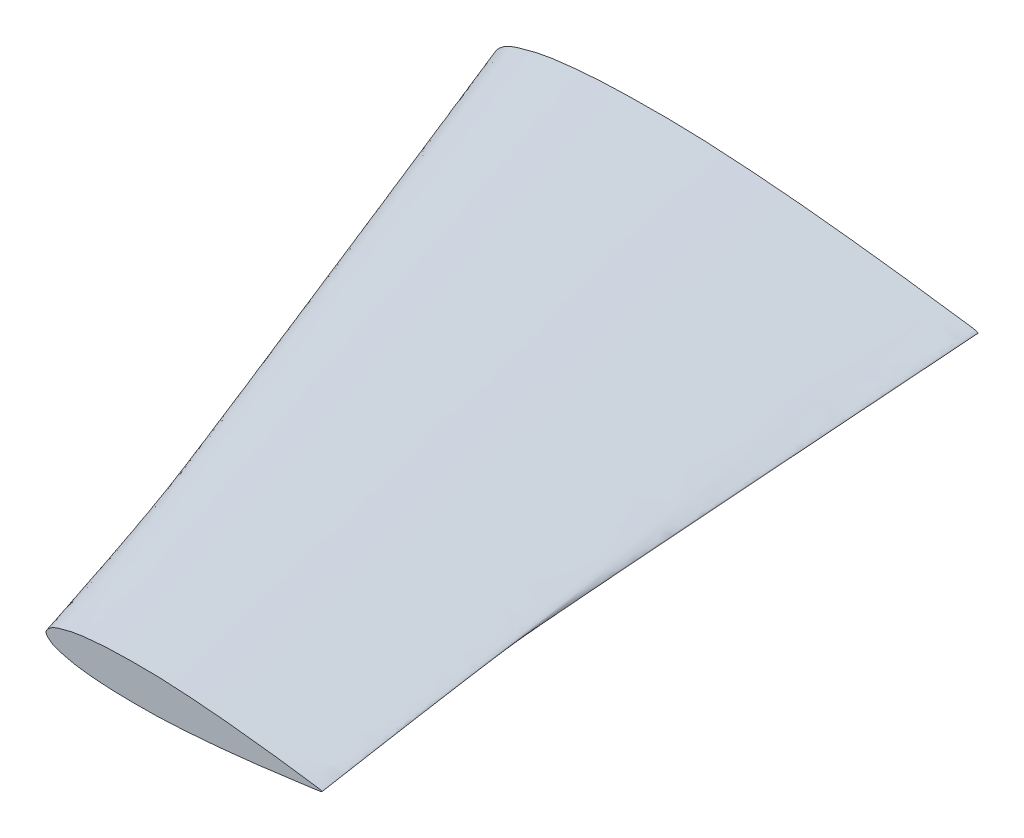
SolidWorks part; units mm, degrees
ref_plane "Front Plane" through (0, 0, 0) normal (0, 0, 1) x (1, 0, 0)
ref_plane "Top Plane" through (0, 0, 0) normal (0, 1, 0) x (1, 0, 0)
ref_plane "Right Plane" through (0, 0, 0) normal (1, 0, 0) x (0, 0, -1)
curve "Curve5"
  spline degree 3 poles (23.9448, -0.2408, 0) (26.1299, 0, 0) (23.9448, 0.2408, 0) (22.5461, 0.4603, 0) (20.2857, 0.7456, 0) (17.7917, 1.0324, 0) (15.2403, 1.2957, 0) (12.7026, 1.4795, 0) (10.1615, 1.6247, 0) (7.6196, 1.6225, 0) (5.4998, 1.5726, 0) (3.8069, 1.4161, 0) (2.7453, 1.2841, 0) (1.8994, 1.0976, 0) (1.2662, 0.917, 0) (0.7044, 0.7371, 0) (0.2766, 0.4441, 0) (-0.1637, 0, 0) (0.2766, -0.4441, 0) (0.7044, -0.7371, 0) (1.2662, -0.917, 0) (1.8994, -1.0976, 0) (2.7453, -1.2841, 0) (3.8069, -1.4161, 0) (5.4998, -1.5726, 0) (7.6196, -1.6225, 0) (10.1615, -1.6247, 0) (12.7026, -1.4795, 0) (15.2403, -1.2957, 0) (17.7917, -1.0324, 0) (20.2857, -0.7456, 0) (22.5461, -0.4603, 0) (23.9448, -0.2408, 0) (26.1299, 0, 0) (23.9448, 0.2408, 0) knots -0.099106 -0.049663 -0.024909 0 0.024909 0.049663 0.099106 0.148459 0.197734 0.246901 0.295993 0.345023 0.394083 0.418697 0.443452 0.456002 0.468731 0.481844 0.489255 0.5 0.510745 0.518156 0.531269 0.543998 0.556548 0.581303 0.605917 0.654977 0.704007 0.753099 0.802266 0.851541 0.900894 0.950337 0.975091 1 1.024909 1.049663 1.099106 periodic
sketch "Sketch2" plane through (0, 0, 0) normal (0, 0, 1) x (1, 0, 0)
  line L0 (0, 0) -> (177.8, 0) construction
  spline S0 degree 3 poles (23.9448, -0.2408) (26.1299, 0) (23.9448, 0.2408) (22.5461, 0.4603) (20.2857, 0.7456) (17.7917, 1.0324) (15.2403, 1.2957) (12.7026, 1.4795) (10.1615, 1.6247) (7.6196, 1.6225) (5.4998, 1.5726) (3.8069, 1.4161) (2.7453, 1.2841) (1.8994, 1.0976) (1.2662, 0.917) (0.7044, 0.7371) (0.2766, 0.4441) (-0.1637, 0) (0.2766, -0.4441) (0.7044, -0.7371) (1.2662, -0.917) (1.8994, -1.0976) (2.7453, -1.2841) (3.8069, -1.4161) (5.4998, -1.5726) (7.6196, -1.6225) (10.1615, -1.6247) (12.7026, -1.4795) (15.2403, -1.2957) (17.7917, -1.0324) (20.2857, -0.7456) (22.5461, -0.4603) (23.9448, -0.2408) (26.1299, 0) (23.9448, 0.2408) knots -0.099106 -0.049663 -0.024909 0 0.024909 0.049663 0.099106 0.148459 0.197734 0.246901 0.295993 0.345023 0.394083 0.418697 0.443452 0.456002 0.468731 0.481844 0.489255 0.5 0.510745 0.518156 0.531269 0.543998 0.556548 0.581303 0.605917 0.654977 0.704007 0.753099 0.802266 0.851541 0.900894 0.950337 0.975091 1 1.024909 1.049663 1.099106 only from (25.4, 0) to (25.4, 0) construction
  spline S1 degree 3 poles (23.9448, -0.2408) (26.1299, 0) (23.9448, 0.2408) (22.5461, 0.4603) (20.2857, 0.7456) (17.7917, 1.0324) (15.2403, 1.2957) (12.7026, 1.4795) (10.1615, 1.6247) (7.6196, 1.6225) (5.4998, 1.5726) (3.8069, 1.4161) (2.7453, 1.2841) (1.8994, 1.0976) (1.2662, 0.917) (0.7044, 0.7371) (0.2766, 0.4441) (-0.1637, 0) (0.2766, -0.4441) (0.7044, -0.7371) (1.2662, -0.917) (1.8994, -1.0976) (2.7453, -1.2841) (3.8069, -1.4161) (5.4998, -1.5726) (7.6196, -1.6225) (10.1615, -1.6247) (12.7026, -1.4795) (15.2403, -1.2957) (17.7917, -1.0324) (20.2857, -0.7456) (22.5461, -0.4603) (23.9448, -0.2408) (26.1299, 0) (23.9448, 0.2408) knots -0.099106 -0.049663 -0.024909 0 0.024909 0.049663 0.099106 0.148459 0.197734 0.246901 0.295993 0.345023 0.394083 0.418697 0.443452 0.456002 0.468731 0.481844 0.489255 0.5 0.510745 0.518156 0.531269 0.543998 0.556548 0.581303 0.605917 0.654977 0.704007 0.753099 0.802266 0.851541 0.900894 0.950337 0.975091 1 1.024909 1.049663 1.099106 only from (25.4, 0) to (25.4, 0) construction
  spline S3 degree 3 poles (167.6134, -1.6853) (182.9092, 0) (167.6134, 1.6853) (157.8229, 3.2223) (142, 5.2193) (124.5417, 7.2266) (106.6823, 9.0702) (88.918, 10.3564) (71.1304, 11.3731) (53.3374, 11.3575) (38.4988, 11.0081) (26.6485, 9.9129) (19.2172, 8.9889) (13.2959, 7.6833) (8.8633, 6.4191) (4.9308, 5.1599) (1.9361, 3.1087) (-1.1458, 0) (1.9361, -3.1087) (4.9308, -5.1599) (8.8633, -6.4191) (13.2959, -7.6833) (19.2172, -8.9889) (26.6485, -9.9129) (38.4988, -11.0081) (53.3374, -11.3575) (71.1304, -11.3731) (88.918, -10.3564) (106.6823, -9.0702) (124.5417, -7.2266) (142, -5.2193) (157.8229, -3.2223) (167.6134, -1.6853) (182.9092, 0) (167.6134, 1.6853) knots -0.099106 -0.049663 -0.024909 0 0.024909 0.049663 0.099106 0.148459 0.197734 0.246901 0.295993 0.345023 0.394083 0.418697 0.443452 0.456002 0.468731 0.481844 0.489255 0.5 0.510745 0.518156 0.531269 0.543998 0.556548 0.581303 0.605917 0.654977 0.704007 0.753099 0.802266 0.851541 0.900894 0.950337 0.975091 1 1.024909 1.049663 1.099106 only from (177.8, 0) to (177.8, 0)
  point P1 (0, 0)
  point P4 (0, 0)
  dimension "D1" = 177.8
ref_plane "Plane1" through (0, 0, 266.7) normal (0, 0, 1) x (1, 0, 0)
sketch "Sketch3" plane through (0, 0, 266.7) normal (0, 0, 1) x (1, 0, 0)
  line L0 (203.2, 0) -> (101.6, 0) construction
  line L1 (0, 0) -> (177.8, 0) construction
  spline S0 degree 3 poles (23.9448, -0.2408) (26.1299, 0) (23.9448, 0.2408) (22.5461, 0.4603) (20.2857, 0.7456) (17.7917, 1.0324) (15.2403, 1.2957) (12.7026, 1.4795) (10.1615, 1.6247) (7.6196, 1.6225) (5.4998, 1.5726) (3.8069, 1.4161) (2.7453, 1.2841) (1.8994, 1.0976) (1.2662, 0.917) (0.7044, 0.7371) (0.2766, 0.4441) (-0.1637, 0) (0.2766, -0.4441) (0.7044, -0.7371) (1.2662, -0.917) (1.8994, -1.0976) (2.7453, -1.2841) (3.8069, -1.4161) (5.4998, -1.5726) (7.6196, -1.6225) (10.1615, -1.6247) (12.7026, -1.4795) (15.2403, -1.2957) (17.7917, -1.0324) (20.2857, -0.7456) (22.5461, -0.4603) (23.9448, -0.2408) (26.1299, 0) (23.9448, 0.2408) knots -0.099106 -0.049663 -0.024909 0 0.024909 0.049663 0.099106 0.148459 0.197734 0.246901 0.295993 0.345023 0.394083 0.418697 0.443452 0.456002 0.468731 0.481844 0.489255 0.5 0.510745 0.518156 0.531269 0.543998 0.556548 0.581303 0.605917 0.654977 0.704007 0.753099 0.802266 0.851541 0.900894 0.950337 0.975091 1 1.024909 1.049663 1.099106 only from (25.4, 0) to (25.4, 0) construction
  spline S1 degree 3 poles (23.9448, -0.2408) (26.1299, 0) (23.9448, 0.2408) (22.5461, 0.4603) (20.2857, 0.7456) (17.7917, 1.0324) (15.2403, 1.2957) (12.7026, 1.4795) (10.1615, 1.6247) (7.6196, 1.6225) (5.4998, 1.5726) (3.8069, 1.4161) (2.7453, 1.2841) (1.8994, 1.0976) (1.2662, 0.917) (0.7044, 0.7371) (0.2766, 0.4441) (-0.1637, 0) (0.2766, -0.4441) (0.7044, -0.7371) (1.2662, -0.917) (1.8994, -1.0976) (2.7453, -1.2841) (3.8069, -1.4161) (5.4998, -1.5726) (7.6196, -1.6225) (10.1615, -1.6247) (12.7026, -1.4795) (15.2403, -1.2957) (17.7917, -1.0324) (20.2857, -0.7456) (22.5461, -0.4603) (23.9448, -0.2408) (26.1299, 0) (23.9448, 0.2408) knots -0.099106 -0.049663 -0.024909 0 0.024909 0.049663 0.099106 0.148459 0.197734 0.246901 0.295993 0.345023 0.394083 0.418697 0.443452 0.456002 0.468731 0.481844 0.489255 0.5 0.510745 0.518156 0.531269 0.543998 0.556548 0.581303 0.605917 0.654977 0.704007 0.753099 0.802266 0.851541 0.900894 0.950337 0.975091 1 1.024909 1.049663 1.099106 only from (25.4, 0) to (25.4, 0) construction
  spline S2 degree 3 poles (197.3791, -0.963) (206.1195, 0) (197.3791, 0.963) (191.7845, 1.8413) (182.7428, 2.9824) (172.7667, 4.1295) (162.5613, 5.183) (152.4103, 5.9179) (142.2459, 6.4989) (132.0785, 6.49) (123.5993, 6.2903) (116.8277, 5.6645) (112.5812, 5.1365) (109.1977, 4.3905) (106.6647, 3.6681) (104.4176, 2.9485) (102.7064, 1.7764) (100.9453, 0) (102.7064, -1.7764) (104.4176, -2.9485) (106.6647, -3.6681) (109.1977, -4.3905) (112.5812, -5.1365) (116.8277, -5.6645) (123.5993, -6.2903) (132.0785, -6.49) (142.2459, -6.4989) (152.4103, -5.9179) (162.5613, -5.183) (172.7667, -4.1295) (182.7428, -2.9824) (191.7845, -1.8413) (197.3791, -0.963) (206.1195, 0) (197.3791, 0.963) knots -0.099106 -0.049663 -0.024909 0 0.024909 0.049663 0.099106 0.148459 0.197734 0.246901 0.295993 0.345023 0.394083 0.418697 0.443452 0.456002 0.468731 0.481844 0.489255 0.5 0.510745 0.518156 0.531269 0.543998 0.556548 0.581303 0.605917 0.654977 0.704007 0.753099 0.802266 0.851541 0.900894 0.950337 0.975091 1 1.024909 1.049663 1.099106 only from (203.2, 0) to (203.2, 0)
  point P2 (101.6, 0)
  dimension "D1" = 101.6
  dimension "D2" = 101.6
loft "Loft1" add profiles "Sketch2", "Sketch3" connector at (46.6022, 11.168, 0) connector at (135.9398, 6.4789, 266.7)
